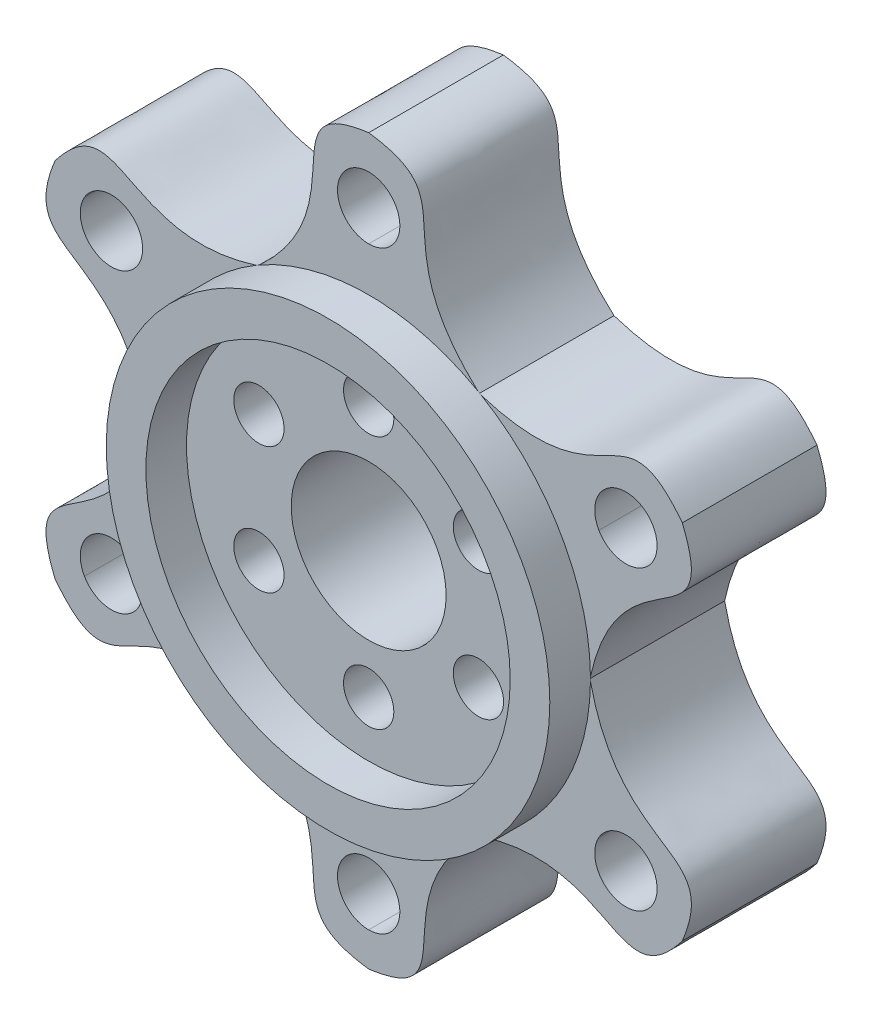
SolidWorks part; units mm, degrees
ref_plane "Front Plane" through (0, 0, 0) normal (0, 0, 1) x (1, 0, 0)
ref_plane "Top Plane" through (0, 0, 0) normal (0, 1, 0) x (1, 0, 0)
ref_plane "Right Plane" through (0, 0, 0) normal (1, 0, 0) x (0, 0, -1)
sketch "Sketch1" plane through (0, 0, 0) normal (0, 0, 1) x (1, 0, 0)
  line L0 (0, -55) -> (0, 55) construction
  line L1 (0, 0) -> (0, 45.72) construction
  circle A0 centre (0, 0) radius 9.779
  circle A1 centre (0, 0) radius 45.72
  circle A2 centre (0, 16.002) radius 3.175
  circle A3 centre (13.8581, 8.001) radius 3.175
  circle A4 centre (13.8581, -8.001) radius 3.175
  circle A5 centre (0, -16.002) radius 3.175
  circle A6 centre (-13.8581, -8.001) radius 3.175
  circle A7 centre (-13.8581, 8.001) radius 3.175
  circle A8 centre (0, 37.5) radius 3.937
  circle A10 centre (32.476, 18.75) radius 3.937
  circle A11 centre (32.476, -18.75) radius 3.937
  circle A12 centre (0, -37.5) radius 3.937
  circle A13 centre (-32.476, -18.75) radius 3.937
  circle A14 centre (-32.476, 18.75) radius 3.937
  point P21 (0, 0)
  point P22 (0, -22.1675)
  point P23 (0, -27.6391)
  point P24 (0, 0)
  point P25 (0, 0)
  point P36 (0, 0)
  point P37 (0, 0)
  point P38 (0, 0)
  dimension "D1" = 19.558
  dimension "D2" = 91.44
  dimension "D3" = 6.35
  dimension "D6" = 7.874
  dimension "D4" = 16.002
  dimension "D8" = 37.5
  dimension "D5" = 6
  dimension "D7" = 6
extrude "Boss-Extrude3" add sketch "Sketch1" along normal blind 17
sketch "Sketch2" plane through (0, 0, 17) normal (0, 0, 1) x (1, 0, 0)
  line L0 (0, -55) -> (0, 55) construction
  line L1 (-32.476, 18.75) -> (0, 37.5) construction
  line L2 (-16.238, 28.125) -> (-4.8895, 8.4689) construction
  line L3 (16.1981, 28.148) -> (4.8496, 8.4918) construction
  line L6 (32.476, -18.75) -> (32.476, 18.75) construction
  line L7 (32.476, 18.75) -> (0, 37.5) construction
  line L8 (55, 0) -> (-55, 0) construction
  circle A0 centre (0, 0) radius 27.94 construction
  circle A1 centre (0, 0) radius 45.72 construction
  circle A2 centre (0, 0) radius 9.779 construction
  circle A3 centre (0, 0) radius 45.72
  spline S0 degree 3 poles (-13.97, 24.1967) (-0.9195, 35.9832) (-13.1193, 43.9586) (0, 45.72) knots 0 0 0 0 1 1 1 1
  spline S1 degree 3 poles (13.97, 24.1967) (0.9195, 35.9832) (13.1193, 43.9586) (0, 45.72) knots 0 0 0 0 1 1 1 1
  spline S2 degree 3 poles (-27.94, 0) (-31.6221, 17.1953) (-44.6289, 10.6177) (-39.5947, 22.86) knots 0 0 0 0 1 1 1 1
  spline S3 degree 3 poles (-13.97, 24.1967) (-30.7026, 18.7879) (-31.5096, 33.3409) (-39.5947, 22.86) knots 0 0 0 0 1 1 1 1
  spline S4 degree 3 poles (-13.97, -24.1967) (-30.7026, -18.7879) (-31.5096, -33.3409) (-39.5947, -22.86) knots 0 0 0 0 1 1 1 1
  spline S5 degree 3 poles (-27.94, 0) (-31.6221, -17.1953) (-44.6289, -10.6177) (-39.5947, -22.86) knots 0 0 0 0 1 1 1 1
  spline S6 degree 3 poles (13.97, -24.1967) (30.7026, -18.7879) (31.5096, -33.3409) (39.5947, -22.86) knots 0 0 0 0 1 1 1 1
  spline S7 degree 3 poles (27.94, 0) (31.6221, -17.1953) (44.6289, -10.6177) (39.5947, -22.86) knots 0 0 0 0 1 1 1 1
  spline S8 degree 3 poles (13.97, -24.1967) (0.9195, -35.9832) (13.1193, -43.9586) (0, -45.72) knots 0 0 0 0 1 1 1 1
  spline S9 degree 3 poles (-13.97, -24.1967) (-0.9195, -35.9832) (-13.1193, -43.9586) (0, -45.72) knots 0 0 0 0 1 1 1 1
  spline S10 degree 3 poles (27.94, 0) (31.6221, 17.1953) (44.6289, 10.6177) (39.5947, 22.86) knots 0 0 0 0 1 1 1 1
  spline S11 degree 3 poles (13.97, 24.1967) (30.7026, 18.7879) (31.5096, 33.3409) (39.5947, 22.86) knots 0 0 0 0 1 1 1 1
  point P5 (-16.238, 28.125)
  point P6 (16.1981, 28.148)
  circle M8 centre (0, 0) radius 45.72
  dimension "D1" = 55.88
  dimension "D2" = 18.796
extrude "Cut-Extrude1" cut sketch "Sketch2" against normal blind 22.86 contours S1 S11 M8 | S5 S2 A3 | S10 S7 A3 | S6 S8 A3 | S9 S4 M8 | S3 S0 M8 region at (38.1245, 0, 17) region at (19.0622, 33.0168, 17) region at (19.0622, -33.0168, 17) region at (-19.0622, 33.0168, 17) region at (-19.0622, -33.0168, 17) region at (-38.1245, 0, 17)
sketch "Sketch4" plane through (0, 0, 17) normal (0, 0, 1) x (1, 0, 0)
  circle A0 centre (0, 0) radius 9.779 construction
  circle A1 centre (0, 0) radius 9.779 construction
  circle A2 centre (0, 0) radius 28
  circle A3 centre (0, 0) radius 23
  dimension "D1" = 56
  dimension "D2" = 46
extrude "Boss-Extrude4" add sketch "Sketch4" along normal blind 5.1308 contours A2 | A3
ref_plane "Plane1" through (0, 0, 0) normal (1, 0, 0) x (0, 0, -1)
ref_plane "Plane2" through (0, 0, 0) normal (-0.5, -0.866, 0) x (-0.866, 0.5, 0)
ref_plane "Plane3" through (0, 0, 0) normal (-0.5, 0.866, 0) x (0.866, 0.5, 0)
split line "Split Line1"
split line "Split Line2"
split line "Split Line3"
ref_axis "Axis1" through (0, 0, 17) along (0, 0, -1)
